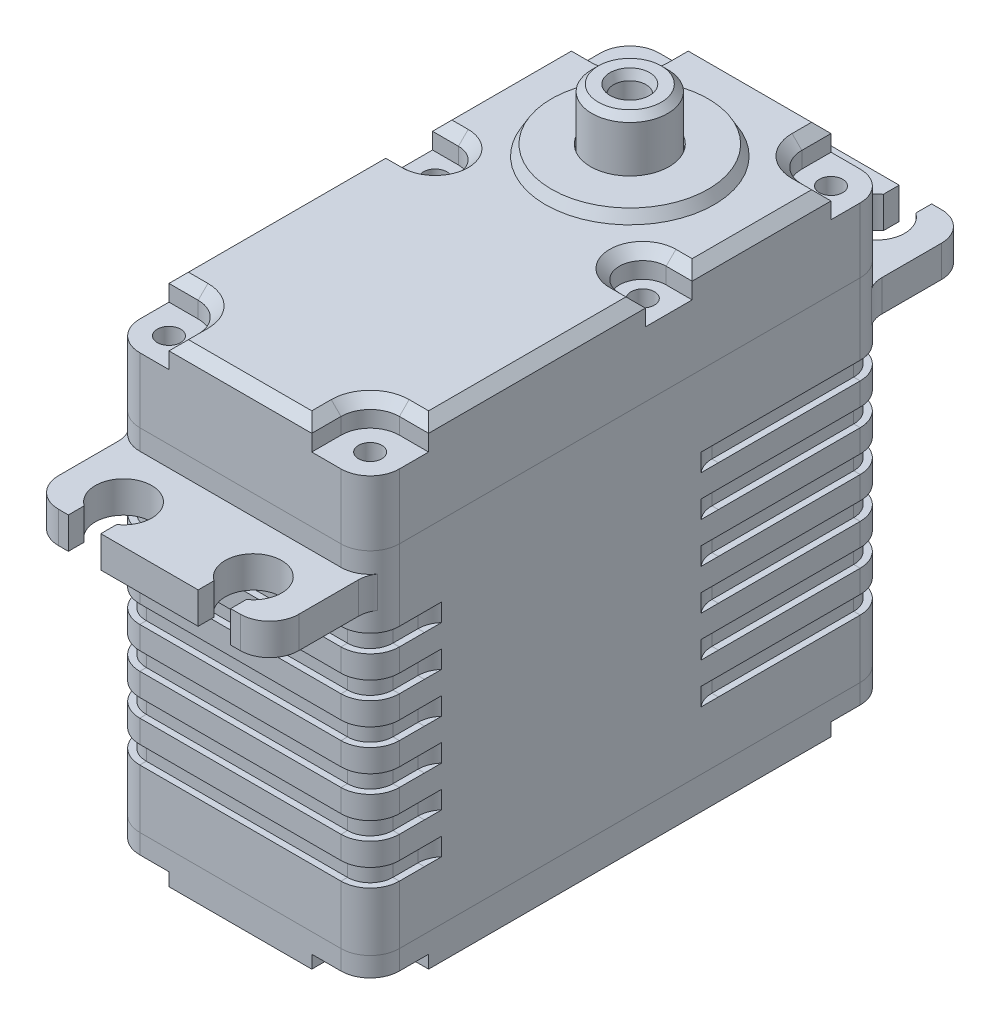
SolidWorks part; units mm, degrees
ref_plane "Front" through (0, 0, 0) normal (0, 0, 1) x (1, 0, 0)
ref_plane "Top" through (0, 0, 0) normal (0, 1, 0) x (1, 0, 0)
ref_plane "Right" through (0, 0, 0) normal (1, 0, 0) x (0, 0, -1)
sketch "Sketch1" plane through (0, 0, 0) normal (0, 1, 0) x (1, 0, 0)
  line L0 (0, 20) -> (0, 0) construction
  line L1 (-7.75, 20) -> (7.75, 20)
  line L2 (-10, 17.75) -> (-10, -17.75)
  line L3 (-7.75, -20) -> (7.75, -20)
  line L4 (10, 17.75) -> (10, -17.75)
  line L5 (0, 0) -> (10, 0) construction
  arc A0 (-10, -17.75) -> (-7.75, -20) centre (-7.75, -17.75) ccw
  arc A1 (7.75, -20) -> (10, -17.75) centre (7.75, -17.75) ccw
  arc A2 (7.75, 20) -> (10, 17.75) centre (7.75, 17.75) cw
  arc A3 (-7.75, 20) -> (-10, 17.75) centre (-7.75, 17.75) ccw
  dimension "D3" = 2.25
  dimension "D1" = 20
  dimension "D2" = 40
extrude "Boss-Extrude1" add sketch "Sketch1" along normal blind 11 and the other way blind 26
sketch "Sketch2" plane through (0, 0, 0) normal (0, 1, 0) x (1, 0, 0)
  line L0 (0, 27) -> (0, 0) construction
  line L1 (0, 0) -> (9.25, 0) construction
  line L3 (-7, 27) -> (7, 27)
  line L4 (-9.25, 24.75) -> (-9.25, -24.75)
  line L5 (-7, -27) -> (7, -27)
  line L6 (9.25, 24.75) -> (9.25, -24.75)
  arc A0 (-9.25, -24.75) -> (-7, -27) centre (-7, -24.75) ccw
  arc A1 (7, -27) -> (9.25, -24.75) centre (7, -24.75) ccw
  arc A2 (7, 27) -> (9.25, 24.75) centre (7, 24.75) cw
  arc A3 (-7, 27) -> (-9.25, 24.75) centre (-7, 24.75) ccw
  dimension "D3" = 2.25
  dimension "D1" = 18.5
  dimension "D2" = 54
extrude "Boss-Extrude2" add sketch "Sketch2" along normal blind 2.43
fillet "Fillet1" radius 2 4 edges at (-9.25, 1.215, 19.4271) (-9.25, 1.215, -19.4271) (9.25, 1.215, -19.4271) (9.25, 1.215, 19.4271)
sketch "Sketch3" plane through (0, 2.43, 0) normal (0, 1, 0) x (1, 0, 0)
  line L0 (0, -27) -> (0, 0) construction
  line L1 (-7, -27) -> (7, -27) construction
  line L2 (0, 0) -> (10, 0) construction
  line L3 (10, -17.75) -> (10, 17.75) construction
  line L4 (-6.25, -25.7799) -> (-6.25, -27)
  line L5 (-6.25, -27) -> (-3.75, -27)
  line L6 (-3.75, -27) -> (-3.75, -25.7799)
  line L7 (3.75, -27) -> (3.75, -25.7799)
  line L8 (6.25, -27) -> (3.75, -27)
  line L9 (6.25, -25.7799) -> (6.25, -27)
  arc A0 (-3.75, -25.7799) -> (-6.25, -25.7799) centre (-5, -24) ccw
  arc A1 (3.75, -25.7799) -> (6.25, -25.7799) centre (5, -24) cw
  dimension "D3" = 4.35
  dimension "D1" = 48
  dimension "D2" = 10
  dimension "D4" = 2.5
extrude "Cut-Extrude1" cut sketch "Sketch3" against normal blind 2.43
mirror "Mirror1" about plane through (0, 0, 0) normal (0, 0, 1) of "Cut-Extrude1"
sketch "Sketch4" plane through (0, 0, 0) normal (1, 0, 0) x (0, 0, -1)
  line L0 (0, 18.0147) -> (0, 0) construction
  line L1 (0, 0) -> (29.9185, 0) construction
  line L2 (10, 23.3424) -> (10, 1.9347) construction
  line L3 (10, 15.8) -> (10, 11)
  line L4 (10, 11) -> (16.5, 11)
  line L5 (-17.75, 11) -> (17.75, 11) construction
  line L6 (16.5, 11) -> (16.0381, 11.8)
  line L7 (16.0381, 11.8) -> (13.025, 11.8)
  line L8 (13.025, 11.8) -> (13.025, 11.2)
  line L9 (13.025, 11.2) -> (12.925, 11.2)
  line L10 (12.925, 11.2) -> (12.925, 15.3)
  line L11 (12.925, 15.3) -> (12.425, 15.8)
  line L12 (12.425, 15.8) -> (10, 15.8)
  dimension "D1" = 10
  dimension "D2" = 45
  dimension "D3" = 0.5
  dimension "D4" = 30
  dimension "D5" = 0.8
  dimension "D6" = 0.2
  dimension "D7" = 0.1
  dimension "D8" = 13
  dimension "D9" = 5.85
  dimension "D10" = 4
revolve "Revolve1" add sketch "Sketch4" angle 360 about L2
sketch "Sketch5" plane through (0, 11, 0) normal (0, 1, 0) x (1, 0, 0)
  line L0 (0, 20) -> (0, 0) construction
  line L1 (-7.75, 20) -> (7.75, 20) construction
  line L2 (0, 0) -> (10, 0) construction
  line L3 (10, -17.75) -> (10, 17.75) construction
  line L4 (-5.5, 20) -> (5.5, 20)
  line L5 (10, -15.5) -> (10, 1.2)
  line L6 (7.75, -20) -> (-7.75, -20) construction
  line L7 (5.5, -20) -> (-5.5, -20)
  line L8 (-10, 17.75) -> (-10, -17.75) construction
  line L9 (-10, 15.5) -> (-10, 4.8)
  line L10 (5.5, 20) -> (5.5, 17.75)
  line L11 (7.75, 15.5) -> (10, 15.5)
  line L12 (-7.75, 15.5) -> (-10, 15.5)
  line L13 (-5.5, 20) -> (-5.5, 17.75)
  line L14 (7.75, -15.5) -> (10, -15.5)
  line L15 (5.5, -20) -> (5.5, -17.75)
  line L16 (-5.5, -20) -> (-5.5, -17.75)
  line L17 (-7.75, -15.5) -> (-10, -15.5)
  line L18 (10, 4.8) -> (8, 4.8)
  line L19 (8, 1.2) -> (10, 1.2)
  line L20 (10, 4.8) -> (10, 15.5)
  line L21 (-8, 1.2) -> (-10, 1.2)
  line L22 (-10, 4.8) -> (-8, 4.8)
  line L23 (-10, 1.2) -> (-10, -15.5)
  arc A0 (5.5, 17.75) -> (7.75, 15.5) centre (7.75, 17.75) ccw
  arc A1 (-5.5, 17.75) -> (-7.75, 15.5) centre (-7.75, 17.75) cw
  arc A2 (5.5, -17.75) -> (7.75, -15.5) centre (7.75, -17.75) cw
  arc A3 (-5.5, -17.75) -> (-7.75, -15.5) centre (-7.75, -17.75) ccw
  arc A4 (8, 4.8) -> (8, 1.2) centre (8, 3) ccw
  arc A5 (-8, 4.8) -> (-8, 1.2) centre (-8, 3) cw
  dimension "D1" = 2.25
  dimension "D2" = 11
  dimension "D3" = 16
  dimension "D4" = 10.7
  dimension "D5" = 16.7
extrude "Cut-Extrude2" cut sketch "Sketch5" against normal blind 2 flip side to cut
sketch "Sketch6" plane through (-10, 0, 0) normal (-1, 0, 0) x (0, 0, 1)
  line L0 (-27, 4) -> (27, 4)
  line L1 (-1.2, 11) -> (15.5, 11) construction
  line L2 (-27, -23) -> (27, -23)
  line L3 (-17.75, -26) -> (17.75, -26) construction
  line L4 (27, 2.43) -> (27, 0) construction
  line L5 (-27, 2.43) -> (-27, 0) construction
  dimension "D1" = 7
  dimension "D2" = 3
split line "Split Line1"
sketch "Sketch7" plane through (0, -26, 0) normal (0, -1, 0) x (1, 0, 0)
  line L4 (7.75, 15.5) -> (10, 15.5)
  line L5 (5.5, 20) -> (5.5, 17.75)
  line L6 (7.75, 20) -> (5.5, 20)
  line L7 (10, 15.5) -> (10, 17.75)
  line L8 (7.75, 15.5) -> (10, 15.5)
  line L9 (5.5, 20) -> (5.5, 17.75)
  line L10 (7.75, 20) -> (5.5, 20)
  line L11 (10, 15.5) -> (10, 17.75)
  line L12 (-5.5, 20) -> (-7.75, 20)
  line L13 (-5.5, 17.75) -> (-5.5, 20)
  line L14 (-10, 15.5) -> (-7.75, 15.5)
  line L15 (-10, 17.75) -> (-10, 15.5)
  line L16 (-5.5, 20) -> (-7.75, 20)
  line L17 (-5.5, 17.75) -> (-5.5, 20)
  line L18 (-10, 15.5) -> (-7.75, 15.5)
  line L19 (-10, 17.75) -> (-10, 15.5)
  line L20 (-7.75, -15.5) -> (-10, -15.5)
  line L21 (-5.5, -20) -> (-5.5, -17.75)
  line L22 (-7.75, -20) -> (-5.5, -20)
  line L23 (-10, -15.5) -> (-10, -17.75)
  line L24 (-7.75, -15.5) -> (-10, -15.5)
  line L25 (-5.5, -20) -> (-5.5, -17.75)
  line L26 (-7.75, -20) -> (-5.5, -20)
  line L27 (-10, -15.5) -> (-10, -17.75)
  line L28 (5.5, -17.75) -> (5.5, -20)
  line L29 (10, -15.5) -> (7.75, -15.5)
  line L30 (10, -17.75) -> (10, -15.5)
  line L31 (5.5, -20) -> (7.75, -20)
  line L32 (5.5, -17.75) -> (5.5, -20)
  line L33 (10, -15.5) -> (7.75, -15.5)
  line L34 (10, -17.75) -> (10, -15.5)
  line L35 (5.5, -20) -> (7.75, -20)
  arc A2 (5.5, 17.75) -> (7.75, 15.5) centre (7.75, 17.75) ccw
  arc A3 (10, 17.75) -> (7.75, 20) centre (7.75, 17.75) ccw
  arc A4 (5.5, 17.75) -> (7.75, 15.5) centre (7.75, 17.75) ccw
  arc A5 (10, 17.75) -> (7.75, 20) centre (7.75, 17.75) ccw
  arc A6 (-7.75, 20) -> (-10, 17.75) centre (-7.75, 17.75) ccw
  arc A7 (-7.75, 15.5) -> (-5.5, 17.75) centre (-7.75, 17.75) ccw
  arc A8 (-7.75, 20) -> (-10, 17.75) centre (-7.75, 17.75) ccw
  arc A9 (-7.75, 15.5) -> (-5.5, 17.75) centre (-7.75, 17.75) ccw
  arc A10 (-5.5, -17.75) -> (-7.75, -15.5) centre (-7.75, -17.75) ccw
  arc A11 (-10, -17.75) -> (-7.75, -20) centre (-7.75, -17.75) ccw
  arc A12 (-5.5, -17.75) -> (-7.75, -15.5) centre (-7.75, -17.75) ccw
  arc A13 (-10, -17.75) -> (-7.75, -20) centre (-7.75, -17.75) ccw
  arc A14 (7.75, -15.5) -> (5.5, -17.75) centre (7.75, -17.75) ccw
  arc A15 (7.75, -20) -> (10, -17.75) centre (7.75, -17.75) ccw
  arc A16 (7.75, -15.5) -> (5.5, -17.75) centre (7.75, -17.75) ccw
  arc A17 (7.75, -20) -> (10, -17.75) centre (7.75, -17.75) ccw
  dimension "D1" = 0
  dimension "D2" = 0
  dimension "D3" = 0
  dimension "D4" = 0
extrude "Cut-Extrude3" cut sketch "Sketch7" against normal blind 1.5
ref_plane "Plane1" through (0, -18.5, 0) normal (0, -1, 0) x (-1, 0, 0)
sketch "Sketch8" plane through (0, -18.5, 0) normal (0, -1, 0) x (-1, 0, 0)
  line L0 (7.75, 20) -> (-7.75, 20) construction
  line L1 (10, -17.75) -> (10, 17.75) construction
  line L2 (-7.75, -20) -> (7.75, -20) construction
  line L3 (-10, 17.75) -> (-10, -17.75) construction
  line L4 (7.75, 20) -> (-7.75, 20) construction
  line L5 (10, -17.75) -> (10, 17.75) construction
  line L6 (-7.75, -20) -> (7.75, -20) construction
  line L7 (-10, 17.75) -> (-10, -17.75) construction
  line L8 (7.75, 19.5) -> (-7.75, 19.5)
  line L9 (-9.5, 17.75) -> (-9.5, 6.8229)
  line L10 (-7.75, -19.5) -> (7.75, -19.5)
  line L11 (9.5, -17.75) -> (9.5, -6.8229)
  line L12 (9.5, 15.8229) -> (9.5, 17.75)
  line L13 (9.5, -17.75) -> (9.5, 17.75) construction
  line L14 (-9.5, -15.8229) -> (-9.5, -17.75)
  line L15 (-9.5, 17.75) -> (-9.5, -17.75) construction
  arc A0 (10, 17.75) -> (7.75, 20) centre (7.75, 17.75) ccw construction
  arc A1 (7.75, -20) -> (10, -17.75) centre (7.75, -17.75) ccw construction
  arc A2 (-10, -17.75) -> (-7.75, -20) centre (-7.75, -17.75) ccw construction
  arc A3 (-7.75, 20) -> (-10, 17.75) centre (-7.75, 17.75) ccw construction
  arc A4 (10, 17.75) -> (7.75, 20) centre (7.75, 17.75) ccw construction
  arc A5 (7.75, -20) -> (10, -17.75) centre (7.75, -17.75) ccw construction
  arc A6 (-10, -17.75) -> (-7.75, -20) centre (-7.75, -17.75) ccw construction
  arc A7 (-7.75, 20) -> (-10, 17.75) centre (-7.75, 17.75) ccw construction
  arc A8 (-7.75, 19.5) -> (-9.5, 17.75) centre (-7.75, 17.75) ccw
  arc A9 (-9.5, -17.75) -> (-7.75, -19.5) centre (-7.75, -17.75) ccw
  arc A10 (7.75, -19.5) -> (9.5, -17.75) centre (7.75, -17.75) ccw
  arc A11 (9.5, 17.75) -> (7.75, 19.5) centre (7.75, 17.75) ccw
  arc A12 (9.5, 15.8229) -> (10, 14.5) centre (11.5, 15.8229) ccw
  arc A13 (9.5, -6.8229) -> (10, -5.5) centre (11.5, -6.8229) cw
  arc A14 (-9.5, -15.8229) -> (-10, -14.5) centre (-11.5, -15.8229) ccw
  arc A15 (-9.5, 6.8229) -> (-10, 5.5) centre (-11.5, 6.8229) cw
  arc A16 (-10, 5.5) -> (-10, -14.5) centre (1.3389, -4.5) ccw
  dimension "D2" = 2
  dimension "D5" = 2
  dimension "D7" = 2
  dimension "D3" = 5.5
  dimension "D4" = 20
  dimension "D6" = 5.5
  dimension "D8" = 20
  dimension "D1" = 0.5
ref_plane "Plane2" through (-10, -18.5, -14.5) normal (-0.6614, 0, 0.75) x (0.75, 0, 0.6614)
sketch "Sketch9" plane through (-10, -18.5, -14.5) normal (-0.6614, 0, 0.75) x (0.75, 0, 0.6614)
  line L0 (0, 0) -> (-0.7, 0)
  line L1 (-0.7, 0) -> (-0.7, 17)
  line L2 (-0.7, 17) -> (0, 17)
  line L3 (0, 17) -> (0, 15.625)
  line L4 (0, 15.625) -> (-0.6, 15.625)
  line L5 (-0.6, 15.625) -> (-0.6, 13.875)
  line L6 (-0.6, 13.875) -> (0, 13.875)
  line L7 (0, 13.875) -> (0, 12.5)
  line L8 (0, 12.5) -> (-0.6, 12.5)
  line L9 (-0.6, 12.5) -> (-0.6, 10.75)
  line L10 (-0.6, 10.75) -> (0, 10.75)
  line L11 (0, 10.75) -> (0, 9.375)
  line L12 (0, 9.375) -> (-0.6, 9.375)
  line L13 (-0.6, 9.375) -> (-0.6, 7.625)
  line L14 (-0.6, 7.625) -> (0, 7.625)
  line L15 (0, 7.625) -> (0, 6.25)
  line L16 (0, 6.25) -> (-0.6, 6.25)
  line L17 (-0.6, 6.25) -> (-0.6, 4.5)
  line L18 (-0.6, 4.5) -> (0, 4.5)
  line L19 (0, 4.5) -> (0, 3.125)
  line L20 (0, 3.125) -> (-0.6, 3.125)
  line L21 (-0.6, 3.125) -> (-0.6, 1.375)
  line L22 (-0.6, 1.375) -> (0, 1.375)
  line L23 (0, 1.375) -> (0, 0)
  line L24 (-1.6197, 0) -> (10.0053, 0) construction
  dimension "D1" = 1.75
  dimension "D2" = 17
  dimension "D3" = 0.6
  dimension "D4" = 0.1
sweep "Cut-Sweep1" cut profiles "Sketch9" path "Sketch8"
chamfer "Chamfer1" distance 0.75 angle 45 24 edges at (5.5, 11, 18.875) (8.875, 11, 15.5) (6.159, 11, 16.159) (0, 11, 20) (-8.875, 11, 15.5) (-5.5, 11, 18.875) (-6.159, 11, 16.159) (-10, 11, 7.15) (-9, 11, -4.8) (-9, 11, -1.2) (-6.2, 11, -3) (-10, 11, -10.15) (-8.875, 11, -15.5) (-6.159, 11, -16.159) (-5.5, 11, -18.875) (0, 11, -20) (5.5, 11, -18.875) (6.159, 11, -16.159) (8.875, 11, -15.5) (10, 11, -10.15) (9, 11, -4.8) (6.2, 11, -3) (9, 11, -1.2) (10, 11, 7.15)
chamfer "Chamfer2" distance 0.5 angle 45 16 edges at (-5.5, -26, -18.875) (-6.159, -26, -16.159) (-8.875, -26, -15.5) (-10, -26, 0) (-8.875, -26, 15.5) (-6.159, -26, 16.159) (-5.5, -26, 18.875) (0, -26, 20) (5.5, -26, 18.875) (6.159, -26, 16.159) (8.875, -26, 15.5) (10, -26, 0) (8.875, -26, -15.5) (6.159, -26, -16.159) (5.5, -26, -18.875) (0, -26, -20)
sketch "Sketch10" plane through (0, 9, 0) normal (0, 1, 0) x (1, 0, 0)
  circle A0 centre (7.75, 17.75) radius 0.9
  circle A1 centre (-7.75, 17.75) radius 0.9
  circle A2 centre (-8, 3) radius 0.9
  circle A3 centre (8, 3) radius 0.9
  circle A4 centre (7.75, -17.75) radius 0.9
  circle A5 centre (-7.75, -17.75) radius 0.9
  dimension "D1" = 1.8
extrude "Cut-Extrude4" cut sketch "Sketch10" against normal up to vertex (5 mm away)
sketch "Sketch11" plane through (0, -24.5, 0) normal (0, -1, 0) x (1, 0, 0)
  circle A0 centre (7.75, 17.75) radius 0.9
  circle A1 centre (-7.75, 17.75) radius 0.9
  circle A2 centre (-7.75, -17.75) radius 0.9
  circle A3 centre (7.75, -17.75) radius 0.9
  dimension "D1" = 1.8
extrude "Cut-Extrude5" cut sketch "Sketch11" against normal up to vertex (1.5 mm away)
hole_wizard "M3 Tapped Hole1" positions "Sketch13" profile "Sketch12" tap size "M3" standard "ISO"
sketch "Sketch13" plane through (0, 15.8, 0) normal (0, 1, 0) x (1, 0, 0)
  point P0 (0, 10)
sketch "Sketch12" plane through (0, 15.8, -10) normal (1, 0, 0) x (0, 0, 1)
  line L0 (0, 0) -> (0, 9.2511)
  line L1 (0, 9.2511) -> (1.25, 8.5)
  line L2 (1.25, 8.5) -> (1.25, 0.6639)
  line L3 (1.25, 0.6639) -> (1.525, 0)
  line L5 (1.525, 0) -> (0, 0)
  line L6 (-1.25, 0.6639) -> (-1.525, 0) construction
  line L10 (0, 9.2511) -> (-1.25, 8.5) construction
  line L11 (0, -6.35) -> (0, 107.95) construction
  dimension "Tap Drill Dia." = 2.5
  dimension "Tap Drill Depth" = 8.5
  dimension "Near C'Sink Dia." = 3.05
  dimension "Near C'Sink Angle" = 45
  dimension "Drill Angle" = 118
cosmetic thread "Hole Thread1" parameters "D1"=6, "D2"=3
hole_wizard "M1.6 Tapped Hole1" positions "Sketch15" profile "Sketch14" tap size "M1.6" standard "ISO"
sketch "Sketch15" plane through (0, 4, 0) normal (0, 1, 0) x (1, 0, 0)
  point P0 (-7.75, 17.75)
  point P3 (7.75, 17.75)
  point P6 (8, 3)
  point P9 (-8, 3)
  point P12 (-7.75, -17.75)
  point P15 (7.75, -17.75)
sketch "Sketch14" plane through (-7.75, 4, -17.75) normal (1, 0, 0) x (0, 0, 1)
  line L0 (0, 0) -> (0, 12.3255)
  line L1 (0, 12.3255) -> (0.625, 11.95)
  line L2 (0.625, 11.95) -> (0.625, 0.4828)
  line L3 (0.625, 0.4828) -> (0.825, 0)
  line L5 (0.825, 0) -> (0, 0)
  line L6 (-0.625, 0.4828) -> (-0.825, 0) construction
  line L10 (0, 12.3255) -> (-0.625, 11.95) construction
  line L11 (0, -6.35) -> (0, 107.95) construction
  dimension "Tap Drill Dia." = 1.25
  dimension "Tap Drill Depth" = 11.95
  dimension "Near C'Sink Dia." = 1.65
  dimension "Near C'Sink Angle" = 45
  dimension "Drill Angle" = 118
cosmetic thread "Hole Thread2" parameters "D1"=10.2, "D2"=1.6
cosmetic thread "Hole Thread3" parameters "D1"=10.2, "D2"=1.6
cosmetic thread "Hole Thread4" parameters "D1"=10.2, "D2"=1.6
cosmetic thread "Hole Thread5" parameters "D1"=10.2, "D2"=1.6
cosmetic thread "Hole Thread6" parameters "D1"=10.2, "D2"=1.6
cosmetic thread "Hole Thread7" parameters "D1"=10.2, "D2"=1.6
hole_wizard "M1.6 Tapped Hole2" positions "Sketch17" profile "Sketch16" tap size "M1.6" standard "ISO"
sketch "Sketch17" plane through (0, -23, 0) normal (0, -1, 0) x (-1, 0, 0)
  point P0 (-7.75, 17.75)
  point P3 (7.75, 17.75)
  point P6 (-7.75, -17.75)
  point P9 (7.75, -17.75)
sketch "Sketch16" plane through (7.75, -23, -17.75) normal (1, 0, 0) x (0, 0, -1)
  line L0 (0, 0) -> (0, 7.3255)
  line L1 (0, 7.3255) -> (0.625, 6.95)
  line L2 (0.625, 6.95) -> (0.625, 0.4828)
  line L3 (0.625, 0.4828) -> (0.825, 0)
  line L5 (0.825, 0) -> (0, 0)
  line L6 (-0.625, 0.4828) -> (-0.825, 0) construction
  line L10 (0, 7.3255) -> (-0.625, 6.95) construction
  line L11 (0, -6.35) -> (0, 107.95) construction
  dimension "Tap Drill Dia." = 1.25
  dimension "Tap Drill Depth" = 6.95
  dimension "Near C'Sink Dia." = 1.65
  dimension "Near C'Sink Angle" = 45
  dimension "Drill Angle" = 118
cosmetic thread "Hole Thread8" parameters "D1"=5.2, "D2"=1.6
cosmetic thread "Hole Thread9" parameters "D1"=5.2, "D2"=1.6
cosmetic thread "Hole Thread10" parameters "D1"=5.2, "D2"=1.6
cosmetic thread "Hole Thread11" parameters "D1"=5.2, "D2"=1.6
sketch "Sketch18" plane through (0, 0, -20) normal (0, 0, -1) x (-1, 0, 0)
  line L0 (0, 0) -> (0, -24.2) construction
  line L1 (5, -26) -> (-5, -26) construction
  line L2 (-3.15, -19.2) -> (3.15, -19.2)
  line L3 (-3.65, -19.7) -> (-3.65, -23.7)
  line L4 (-3.15, -24.2) -> (3.15, -24.2)
  line L5 (3.65, -19.7) -> (3.65, -23.7)
  arc A0 (-3.65, -23.7) -> (-3.15, -24.2) centre (-3.15, -23.7) ccw
  arc A1 (-3.15, -19.2) -> (-3.65, -19.7) centre (-3.15, -19.7) ccw
  arc A2 (3.15, -19.2) -> (3.65, -19.7) centre (3.15, -19.7) cw
  arc A3 (3.15, -24.2) -> (3.65, -23.7) centre (3.15, -23.7) ccw
  dimension "D1" = 0.5
  dimension "D2" = 5
  dimension "D3" = 1.8
  dimension "D4" = 7.3
extrude "Boss-Extrude3" add sketch "Sketch18" along normal blind 1
sketch "Sketch19" plane through (0, 0, -21) normal (0, 0, -1) x (-1, 0, 0)
  line L0 (0, -20.325) -> (0, -19.2) construction
  line L1 (-1.575, -20.325) -> (1.575, -20.325)
  line L2 (-2.875, -21.625) -> (-2.875, -21.775)
  line L3 (-1.575, -23.075) -> (1.575, -23.075)
  line L4 (2.875, -21.625) -> (2.875, -21.775)
  line L5 (3.15, -19.2) -> (-3.15, -19.2) construction
  line L6 (2.875, -21.7) -> (3.65, -21.7) construction
  line L7 (3.65, -23.7) -> (3.65, -19.7) construction
  arc A0 (1.575, -20.325) -> (2.875, -21.625) centre (1.575, -21.625) cw
  arc A1 (1.575, -23.075) -> (2.875, -21.775) centre (1.575, -21.775) ccw
  arc A2 (-2.875, -21.775) -> (-1.575, -23.075) centre (-1.575, -21.775) ccw
  arc A3 (-1.575, -20.325) -> (-2.875, -21.625) centre (-1.575, -21.625) ccw
  dimension "D3" = 1.3
  dimension "D1" = 5.75
  dimension "D2" = 2.75
extrude "Boss-Extrude4" add sketch "Sketch19" along normal blind 3 draft 5
sketch "Sketch20" plane through (0, 0, -24) normal (0, 0, -1) x (-1, 0, 0)
  line L0 (-1.525, -21.7) -> (1.525, -21.7) construction
  line L1 (2.875, -21.7) -> (3.65, -21.7) construction
  line L2 (0, -20.325) -> (0, -19.2) construction
  circle A0 centre (-1.525, -21.7) radius 0.75
  circle A1 centre (1.525, -21.7) radius 0.75
  circle A2 centre (0, -21.7) radius 0.75
  point P4 (0, -21.7)
  dimension "D2" = 1.5
  dimension "D1" = 3.05
extrude "Boss-Extrude5" add sketch "Sketch20" along normal blind 0.5
fillet "Fillet2" radius 0.25 24 edges at (2.3086, -22.5086, -24) (2.6125, -21.7, -24) (2.3086, -20.8914, -24) (0, -20.5875, -24) (-2.3086, -20.8914, -24) (-2.6125, -21.7, -24) (-2.3086, -22.5086, -24) (2.4942, -22.6942, -21) (2.875, -21.7, -21) (2.4942, -20.7058, -21) (0, -20.325, -21) (-2.4942, -20.7058, -21) (-2.875, -21.7, -21) (-2.4942, -22.6942, -21) (3.5036, -24.0536, -21) (3.65, -21.7, -21) (3.5036, -19.3464, -21) (0, -19.2, -21) (-3.5036, -19.3464, -21) (-3.65, -21.7, -21) (-3.5036, -24.0536, -21) (0, -22.8125, -24) (0, -23.075, -21) (0, -24.2, -21)
sketch "Sketch21" plane through (0, 11, 0) normal (0, 1, 0) x (1, 0, 0)
  line L0 (0, 3.5) -> (0, -19.25) construction
  line L1 (-4.75, -19.25) -> (4.75, -19.25) construction
  line L2 (0, -7.875) -> (-9.25, -7.875) construction
  line L3 (-9.25, 0.45) -> (-9.25, -14.75) construction
  circle A0 centre (0, 10) radius 6.5 construction
